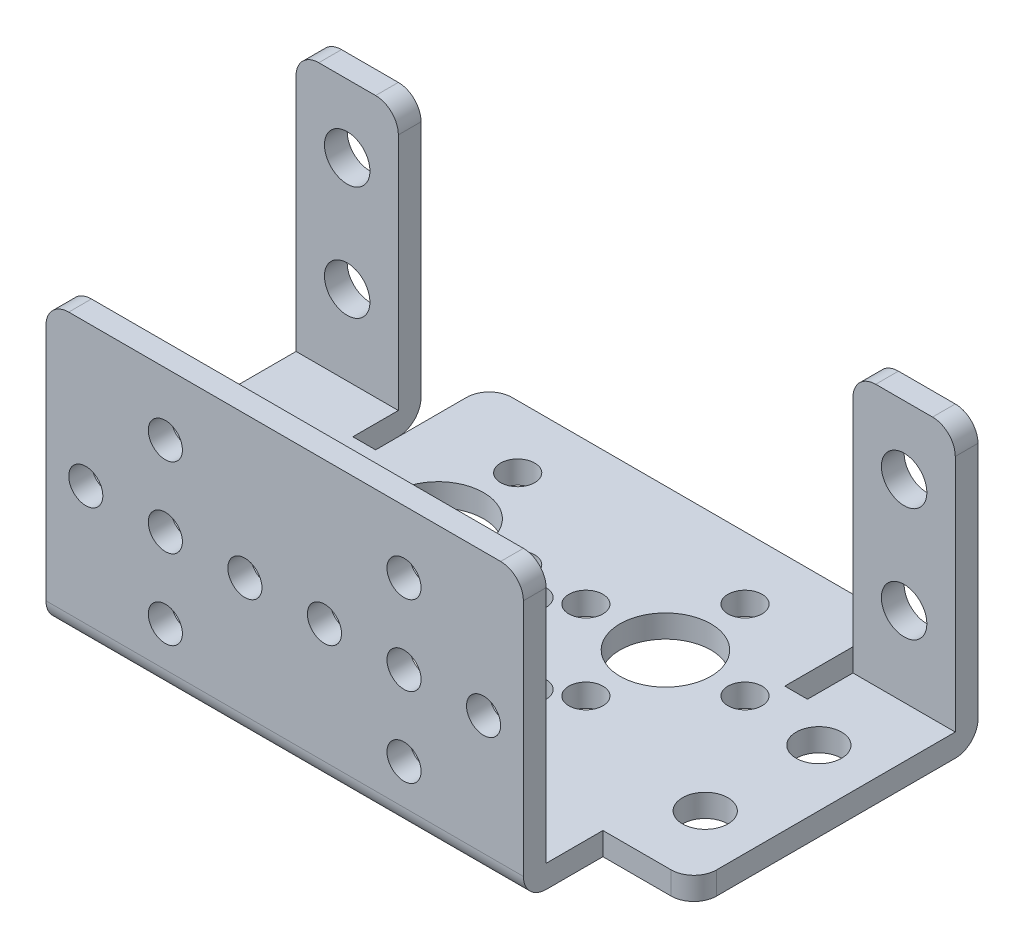
SolidWorks part; units mm, degrees
ref_plane "Front Plane" through (0, 0, 0) normal (0, 0, 1) x (1, 0, 0)
ref_plane "Top Plane" through (0, 0, 0) normal (0, 1, 0) x (1, 0, 0)
ref_plane "Right Plane" through (0, 0, 0) normal (1, 0, 0) x (0, 0, -1)
sketch "Sketch1" plane through (0, 0, 0) normal (0, 0, 1) x (1, 0, 0)
  line L1 (0, 0) -> (42, 0)
  line L2 (0, 0) -> (0, 25)
  line L3 (0, 25) -> (42, 25)
  line L4 (42, 0) -> (42, 25)
  circle A0 centre (10.5, 12.5) radius 1.5
  circle A1 centre (10.5, 19.5) radius 1.5
  circle A2 centre (17.5, 12.5) radius 1.5
  circle A3 centre (3.5, 12.5) radius 1.5
  circle A4 centre (10.5, 5.5) radius 1.5
  circle A5 centre (31.5, 12.5) radius 1.5
  circle A6 centre (38.5, 12.5) radius 1.5
  circle A7 centre (31.5, 19.5) radius 1.5
  circle A8 centre (24.5, 12.5) radius 1.5
  circle A9 centre (31.5, 5.5) radius 1.5
  point P25 (0, 0)
  point P26 (0, 0)
  point P27 (0, 0)
  point P28 (0, 0)
  dimension "D3" = 3
  dimension "D1" = 42
  dimension "D2" = 25
  dimension "D4" = 7
  dimension "D5" = 7
  dimension "D6" = 7
  dimension "D7" = 7
  dimension "D8" = 7
  dimension "D9" = 7
  dimension "D10" = 12.5
  dimension "D11" = 10.5
  dimension "D12" = 10.5
extrude "Boss-Extrude1" add sketch "Sketch1" against normal blind 2
sketch "Sketch2" plane through (0, 0, 0) normal (0, -1, 0) x (1, 0, 0)
  line L0 (0, -32) -> (0, -36)
  line L1 (0, 0) -> (42, 0)
  line L2 (0, 0) -> (0, -7)
  line L3 (0, -36) -> (42, -36)
  line L4 (42, 0) -> (42, -7)
  line L5 (-6, -7) -> (0, -7)
  line L6 (-8, -9) -> (-8, -32)
  line L7 (-8, -32) -> (0, -32)
  line L8 (50, -9) -> (50, -32)
  line L9 (42, -7) -> (48, -7)
  line L10 (42, -32) -> (50, -32)
  line L11 (42, -32) -> (42, -36)
  line L12 (21, -2) -> (21, -36) construction
  line L13 (0, -2) -> (42, -2) construction
  line L14 (19.5, -23.5) -> (21, -23.5) construction
  line L15 (22.5, -23.5) -> (21, -23.5) construction
  circle A0 centre (45, -13) radius 2
  circle A1 centre (45, -23) radius 2
  circle A2 centre (-3, -13) radius 2
  circle A3 centre (-3, -23) radius 2
  arc A4 (-6, -7) -> (-8, -9) centre (-6, -9) ccw
  arc A5 (48, -7) -> (50, -9) centre (48, -9) cw
  circle A6 centre (11, -23.5) radius 4
  circle A7 centre (31, -23.5) radius 4
  circle A8 centre (21, -14.5) radius 4
  circle A9 centre (11, -16.5) radius 1.5
  circle A10 centre (11, -30.5) radius 1.5
  circle A11 centre (18, -23.5) radius 1.5
  circle A12 centre (4, -23.5) radius 1.5
  circle A13 centre (31, -30.5) radius 1.5
  circle A14 centre (24, -23.5) radius 1.5
  circle A15 centre (31, -16.5) radius 1.5
  circle A16 centre (38, -23.5) radius 1.5
  circle A17 centre (21, -21.5) radius 1.5
  circle A18 centre (21, -7.5) radius 1.5
  circle A19 centre (28, -14.5) radius 1.5
  circle A20 centre (14, -14.5) radius 1.5
  point P24 (-8, -7)
  point P27 (50, -7)
  point P63 (21, -23.5)
  dimension "D6" = 2
  dimension "D7" = 4
  dimension "D8" = 10
  dimension "D10" = 5
  dimension "D11" = 5
  dimension "D12" = 8
  dimension "D13" = 14.5
  dimension "D14" = 12.5
  dimension "D15" = 3
  dimension "D1" = 36
  dimension "D2" = 25
  dimension "D3" = 7
  dimension "D4" = 58
  dimension "D5" = 8
  dimension "D9" = 6
  dimension "D16" = 7
  dimension "D17" = 7
  dimension "D18" = 7
  dimension "D19" = 7
  dimension "D20" = 7
  dimension "D21" = 7
  dimension "D22" = 7
  dimension "D23" = 7
  dimension "D24" = 7
  dimension "D25" = 7
  dimension "D26" = 20
  dimension "D27" = 7
extrude "Boss-Extrude2" add sketch "Sketch2" against normal blind 2
sketch "Sketch3" plane through (0, 0, 0) normal (0, -1, 0) x (1, 0, 0)
sketch "Sketch4" plane through (0, 0, 0) normal (0, -1, 0) x (1, 0, 0)
  line L0 (39, -36) -> (39, -26)
  line L1 (0, -36) -> (42, -36) construction
  line L2 (39, -26) -> (41, -26)
  line L3 (41, -26) -> (41, -32)
  line L4 (41, -32) -> (42, -32)
  line L17 (42, 0) -> (0, 0)
  line L18 (0, 0) -> (0, -7)
  line L19 (0, -7) -> (-6, -7)
  line L20 (-8, -9) -> (-8, -32)
  line L21 (-8, -32) -> (0, -32)
  line L22 (0, -32) -> (0, -36)
  line L23 (0, -36) -> (42, -36)
  line L24 (42, -36) -> (42, -32)
  line L25 (42, -32) -> (50, -32)
  line L26 (50, -32) -> (50, -9)
  line L27 (48, -7) -> (42, -7)
  line L28 (42, -7) -> (42, 0)
  line L35 (39, -36) -> (42, -36)
  line L36 (42, -36) -> (42, -32)
  arc A2 (-6, -7) -> (-8, -9) centre (-6, -9) ccw
  arc A3 (50, -9) -> (48, -7) centre (48, -9) ccw
  point P14 (0, 0)
  point P15 (41, -32)
  dimension "D1" = 10
  dimension "D2" = 2
  dimension "D3" = 1
  dimension "D4" = 0
extrude "Cut-Extrude1" cut sketch "Sketch4" against normal blind 2
ref_plane "Plane1" through (21, 0, 0) normal (1, 0, 0) x (0, 0, -1)
mirror "Mirror1" about plane through (21, 0, 0) normal (1, 0, 0) of "Cut-Extrude1"
fillet "Fillet1" radius 2 1 edges at (3, 1, -36)
fillet "Fillet2" radius 2 1 edges at (39, 1, -36)
fillet "Fillet3" radius 2 1 edges at (21, 0, 0)
fillet "Fillet4" radius 2 1 edges at (42, 25, -1)
fillet "Fillet5" radius 2 1 edges at (0, 25, -1)
sketch "Sketch5" plane through (0, 0, -32) normal (0, 0, -1) x (-1, 0, 0)
  line L1 (8, 0) -> (-1, 0)
  line L2 (8, 0) -> (8, 23)
  line L3 (6, 25) -> (1, 25)
  line L4 (-1, 0) -> (-1, 23)
  arc A0 (8, 23) -> (6, 25) centre (6, 23) ccw
  arc A1 (1, 25) -> (-1, 23) centre (1, 23) ccw
  dimension "D1" = 2
  dimension "D2" = 9
  dimension "D3" = 25
extrude "Boss-Extrude3" add sketch "Sketch5" against normal blind 2
mirror "Mirror2" about plane through (21, 0, 0) normal (1, 0, 0) of "Boss-Extrude3"
fillet "Fillet6" radius 2 1 edges at (45.5, 0, -32)
fillet "Fillet7" radius 2 1 edges at (-3.5, 0, -32)
sketch "Sketch6" plane through (0, 0, -32) normal (0, 0, -1) x (-1, 0, 0)
  line L0 (3.5, 25) -> (3.5, 0) construction
  line L1 (6, 25) -> (1, 25) construction
  circle A0 centre (3.5, 19) radius 2
  circle A1 centre (3.5, 9) radius 2
  point P8 (0, 0)
  point P9 (0, 0)
  dimension "D2" = 4
  dimension "D1" = 10
  dimension "D3" = 6
extrude "Cut-Extrude2" cut sketch "Sketch6" against normal blind 2
mirror "Mirror3" about plane through (21, 0, 0) normal (1, 0, 0) of "Cut-Extrude2"
